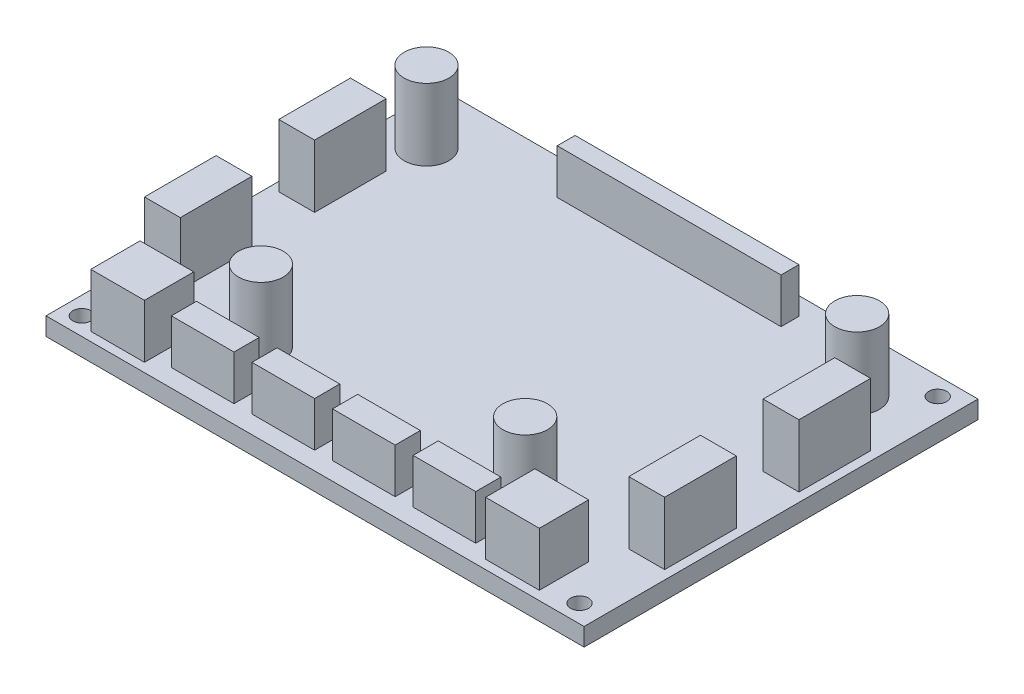
SolidWorks part; units mm, degrees
ref_plane "Front Plane" through (0, 0, 0) normal (0, 0, 1) x (1, 0, 0)
ref_plane "Top Plane" through (0, 0, 0) normal (0, 1, 0) x (1, 0, 0)
ref_plane "Right Plane" through (0, 0, 0) normal (1, 0, 0) x (0, 0, -1)
sketch "Sketch1" plane through (0, 0, 0) normal (0, 1, 0) x (1, 0, 0)
  line L0 (-75.1653, 69.85) -> (-75.1653, 0)
  line L1 (-75.1653, 0) -> (20.2434, 0)
  line L2 (20.2434, 0) -> (20.2434, 69.85)
  line L3 (20.2434, 69.85) -> (-75.1653, 69.85)
  line L6 (-73.5778, 52.3875) -> (-67.2278, 52.3875)
  line L7 (-73.5778, 52.3875) -> (-73.5778, 39.6875)
  line L8 (-73.5778, 39.6875) -> (-67.2278, 39.6875)
  line L9 (-67.2278, 52.3875) -> (-67.2278, 39.6875)
  line L10 (-73.5778, 28.575) -> (-67.2278, 28.575)
  line L11 (-73.5778, 28.575) -> (-73.5778, 15.875)
  line L12 (-73.5778, 15.875) -> (-67.2278, 15.875)
  line L13 (-67.2278, 28.575) -> (-67.2278, 15.875)
  line L14 (12.3059, 28.575) -> (12.3059, 15.875)
  line L15 (18.6559, 15.875) -> (12.3059, 15.875)
  line L16 (18.6559, 28.575) -> (18.6559, 15.875)
  line L17 (18.6559, 28.575) -> (12.3059, 28.575)
  line L18 (12.3059, 52.3875) -> (12.3059, 39.6875)
  line L19 (18.6559, 39.6875) -> (12.3059, 39.6875)
  line L20 (18.6559, 52.3875) -> (18.6559, 39.6875)
  line L21 (18.6559, 52.3875) -> (12.3059, 52.3875)
  line L22 (-41.8278, 7.6395) -> (-41.8278, 3.175)
  line L23 (-68.8153, 10.3273) -> (-59.2903, 10.3273)
  line L24 (-68.8153, 10.3273) -> (-68.8153, 1.5875)
  line L25 (-68.8153, 1.5875) -> (-59.2903, 1.5875)
  line L26 (-59.2903, 10.3273) -> (-59.2903, 1.5875)
  line L27 (-56.1153, 7.6395) -> (-45.0028, 7.6395)
  line L28 (-56.1153, 7.6395) -> (-56.1153, 3.175)
  line L29 (-56.1153, 3.175) -> (-45.0028, 3.175)
  line L30 (-45.0028, 7.6395) -> (-45.0028, 3.175)
  line L31 (-41.8278, 7.6395) -> (-30.7153, 7.6395)
  line L32 (-30.7153, 7.6395) -> (-30.7153, 3.175)
  line L33 (-41.8278, 3.175) -> (-30.7153, 3.175)
  line L34 (-27.5403, 7.6395) -> (-27.5403, 3.175)
  line L35 (-27.5403, 7.6395) -> (-16.4278, 7.6395)
  line L36 (-16.4278, 7.6395) -> (-16.4278, 3.175)
  line L37 (-27.5403, 3.175) -> (-16.4278, 3.175)
  line L38 (-13.2528, 7.6395) -> (-13.2528, 3.175)
  line L39 (-13.2528, 7.6395) -> (-2.1403, 7.6395)
  line L40 (-2.1403, 7.6395) -> (-2.1403, 3.175)
  line L41 (-13.2528, 3.175) -> (-2.1403, 3.175)
  line L43 (1.1934, 1.5875) -> (10.7184, 1.5875)
  line L44 (1.1934, 1.5875) -> (1.1934, 10.3273)
  line L45 (1.1934, 10.3273) -> (10.7184, 10.3273)
  line L46 (10.7184, 1.5875) -> (10.7184, 10.3273)
  line L47 (-48.0191, 63.5) -> (-8.3316, 63.5)
  line L48 (-48.0191, 63.5) -> (-48.0191, 66.675)
  line L49 (-48.0191, 66.675) -> (-8.3316, 66.675)
  line L50 (-8.3316, 63.5) -> (-8.3316, 66.675)
  circle A0 centre (-71.9903, 66.675) radius 1.5875
  circle A1 centre (16.2747, 3.175) radius 1.5875
  circle A2 centre (16.2747, 66.675) radius 1.5875
  circle A3 centre (-71.9903, 3.175) radius 1.5875
  circle A4 centre (-51.3528, 14.2875) radius 3.9687
  circle A5 centre (-4.486, 14.2875) radius 3.9688
  circle A6 centre (9.1309, 59.5312) radius 3.9688
  circle A7 centre (-67.2278, 59.5312) radius 3.9687
  dimension "D3" = 3.9688
  dimension "D5" = 3.175
  dimension "D6" = 3.175
  dimension "D22" = 7.9375
  dimension "D23" = 7.9375
  dimension "D25" = 7.9375
  dimension "D28" = 7.9375
  dimension "D1" = 3.175
  dimension "D2" = 3.175
  dimension "D4" = 3.175
  dimension "D7" = 17.4625
  dimension "D8" = 1.5875
  dimension "D9" = 28.575
  dimension "D10" = 1.5875
  dimension "D11" = 6.35
  dimension "D12" = 4
  dimension "D13" = 1.5875
  dimension "D14" = 3.175
  dimension "D15" = 3.175
  dimension "D16" = 44.45
  dimension "D17" = 9.525
  dimension "D18" = 28.575
  dimension "D19" = 3.175
  dimension "D20" = 14.2875
  dimension "D21" = 23.8125
  dimension "D24" = 14.2875
  dimension "D26" = 11.1125
  dimension "D27" = 10.3187
  dimension "D29" = 7.9375
extrude "Boss-Extrude1" add sketch "Sketch1" along normal blind 3.175 contours L3 L0 L1 L2
extrude "Boss-Extrude2" add sketch "Sketch1<4>" along normal blind 15.875 contours A7 | A4 | A5 | A6
sketch "Sketch1<4>" plane through (0, 0, 0) normal (0, 1, 0) x (1, 0, 0) same geometry as "Sketch1"
extrude "Boss-Extrude3" add sketch "Sketch1<5>" along normal blind 14.2875 contours L13 L12 L11 L10 | L6 L9 L8 L7 | L14 L15 L16 L17 | L18 L19 L20 L21
sketch "Sketch1<5>" plane through (0, 0, 0) normal (0, 1, 0) x (1, 0, 0) same geometry as "Sketch1"
extrude "Boss-Extrude4" add sketch "Sketch1<6>" along normal blind 11.1125 contours L49 L50 L47 L48
sketch "Sketch1<6>" plane through (0, 0, 0) normal (0, 1, 0) x (1, 0, 0) same geometry as "Sketch1"
extrude "Cut-Extrude4" cut sketch "Sketch1<8>" along normal through all contours A0 | A3 | A2 | A1
sketch "Sketch1<8>" plane through (0, 0, 0) normal (0, 1, 0) x (1, 0, 0) same geometry as "Sketch1"
extrude "Boss-Extrude5" add sketch "Sketch1<9>" along normal blind 11.1125 contours L22 L33 L32 L31 | L34 L37 L36 L35 | L38 L41 L40 L39 | L29 L30 L27 L28 region at (-36.2716, 0, -5.4072) region at (-21.9841, 0, -5.4072) region at (-7.6966, 0, -5.4072)
sketch "Sketch1<9>" plane through (0, 0, 0) normal (0, 1, 0) x (1, 0, 0) same geometry as "Sketch1"
extrude "Boss-Extrude6" add sketch "Sketch1<10>" along normal blind 12.7 contours L23 L26 L25 L24 | L45 L46 L43 L44
sketch "Sketch1<10>" plane through (0, 0, 0) normal (0, 1, 0) x (1, 0, 0) same geometry as "Sketch1"
